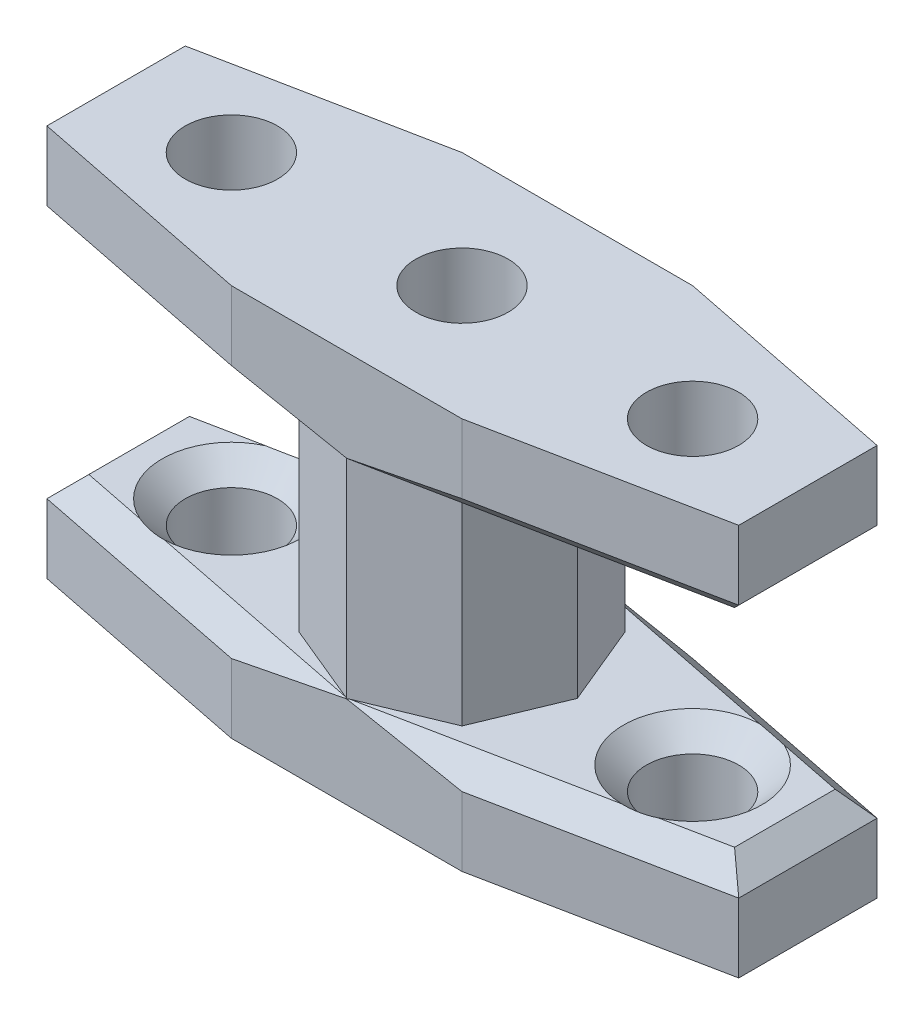
SolidWorks part; units mm, degrees
material "Plain Carbon Steel"
ref_plane "Front Plane" through (0, 0, 0) normal (0, 0, 1) x (1, 0, 0)
ref_plane "Top Plane" through (0, 0, 0) normal (0, 1, 0) x (1, 0, 0)
ref_plane "Right Plane" through (0, 0, 0) normal (1, 0, 0) x (0, 0, -1)
sketch "Sketch1" plane through (0, 0, 0) normal (0, 1, 0) x (1, 0, 0)
  line L0 (0, 2.6897) -> (14.0646, 2.6897) construction
  line L5 (-5, -2.3103) -> (5, -2.3103)
  line L6 (-15, -0.3103) -> (-15, 5.6897)
  line L7 (-5, 7.6897) -> (5, 7.6897)
  line L8 (15, -0.3103) -> (15, 5.6897)
  line L9 (-14.494, -7.6897) -> (14.494, 7.6897) construction
  line L10 (0, -13.7179) -> (0, 19.0973) construction
  line L11 (0, 2.6897) -> (0, 7.6897) construction
  line L12 (5, 7.6897) -> (15, 5.6897)
  line L13 (5, -2.3103) -> (15, -0.3103)
  line L14 (-5, -2.3103) -> (-15, -0.3103)
  line L15 (-5, 7.6897) -> (-15, 5.6897)
  circle A0 centre (10, 2.6897) radius 2
  circle A1 centre (0, 2.6897) radius 2
  circle A2 centre (-10, 2.6897) radius 2
  point P0 (0, 0)
  dimension "D5" = 4
  dimension "D6" = 4
  dimension "D1" = 10
  dimension "D2" = 15
  dimension "D3" = 2
  dimension "D4" = 10
  dimension "D7" = 10
extrude "Boss-Extrude1" add sketch "Sketch1" along normal blind 4
sketch "Sketch2" plane through (0, 0, 0) normal (0, 1, 0) x (1, 0, 0)
  line L1 (0, -2.3103) -> (3.5355, -0.8458)
  line L2 (3.5355, -0.8458) -> (5, 2.6897)
  line L3 (5, 2.6897) -> (3.5355, 6.2252)
  line L4 (3.5355, 6.2252) -> (0, 7.6897)
  line L5 (0, 7.6897) -> (-3.5355, 6.2252)
  line L6 (-3.5355, 6.2252) -> (-5, 2.6897)
  line L7 (-5, 2.6897) -> (-3.5355, -0.8458)
  line L8 (-3.5355, -0.8458) -> (0, -2.3103)
  circle A0 centre (0, 2.6897) radius 4.6194 construction
  point P1 (0, 0)
  point P12 (0, 0)
extrude "Boss-Extrude2" add sketch "Sketch2" along normal blind 9 from surface starting at face at (0, 4, -0.6897)
ref_plane "Plane1" through (0, 8.5, 0) normal (0, 1, 0) x (1, 0, 0)
mirror "Mirror1" about plane through (0, 8.5, 0) normal (0, 1, 0) of "Boss-Extrude1"
chamfer "Chamfer2" distance 1 angle 45 7 edges at (10, 4, -6.6897) (15, 4, -2.6897) (10, 4, 1.3103) (10, 4, -0.6897) (10, 13, 1.3103) (10, 13, -6.6897) (15, 13, -2.6897)
chamfer "Chamfer3" distance 1 angle 45 7 edges at (-10, 4, -4.6897) (-10, 13, -6.6897) (-15, 13, -2.6897) (-10, 13, 1.3103) (-10, 4, -6.6897) (-15, 4, -2.6897) (-10, 4, 1.3103)
sketch "Sketch4" plane through (0, 4, 0) normal (0, -1, 0) x (1, 0, 0)
extrude "Cut-Extrude2" cut sketch "Sketch1<2>" against normal blind 9 and the other way blind 10 contours A1 region at (0, 0, -2.6897)
sketch "Sketch1<2>" plane through (0, 0, 0) normal (0, 1, 0) x (1, 0, 0) same geometry as "Sketch1"
sketch "Sketch6" plane through (0, 13, 0) normal (0, 1, 0) x (1, 0, 0)
  circle A0 centre (0, 2.6897) radius 2
extrude "Cut-Extrude3" cut sketch "Sketch6" against normal blind 17
